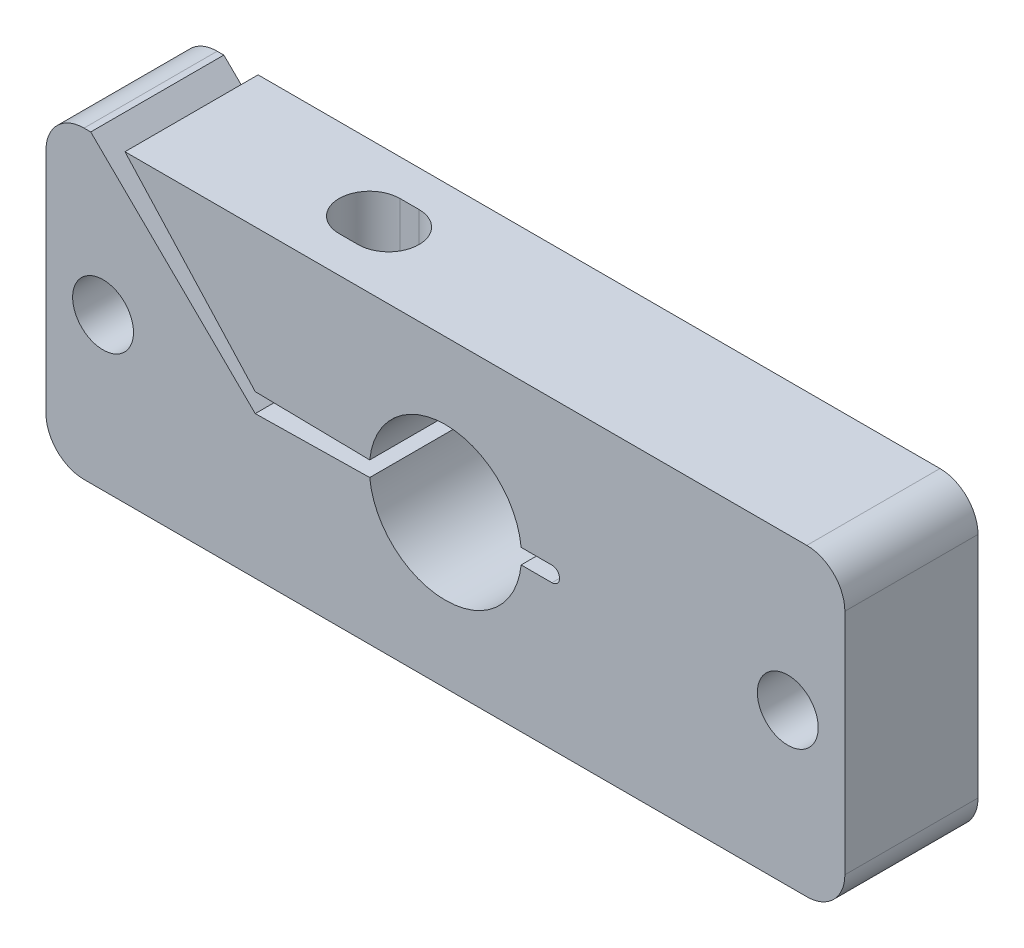
SolidWorks part; units mm, degrees
ref_plane "Front Plane" through (0, 0, 0) normal (0, 0, 1) x (1, 0, 0)
ref_plane "Top Plane" through (0, 0, 0) normal (0, 1, 0) x (1, 0, 0)
ref_plane "Right Plane" through (0, 0, 0) normal (1, 0, 0) x (0, 0, -1)
sketch "Sketch1" plane through (0, 0, 0) normal (0, 0, 1) x (1, 0, 0)
  line L0 (-43.3338, 0) -> (30.2546, 0) construction
  line L1 (-10, 0) -> (-19.1197, 9.4437) construction
  line L2 (-21, 8) -> (-18.6497, 8)
  line L3 (-21, 8) -> (-21, -8)
  line L4 (-21, -8) -> (21, -8)
  line L5 (21, 8) -> (21, -8)
  line L6 (-10, 0.5) -> (-3.9799, 0.4)
  line L7 (-10, 0.5) -> (-10, -0.5) construction
  line L8 (-10, -0.5) -> (-3.9799, -0.4)
  line L9 (6, 0.4) -> (6, -0.4)
  line L10 (-10, 0.5) -> (-16.8484, 8)
  line L11 (-10, -0.5) -> (-18.6497, 8)
  line L12 (3.9799, 0.4) -> (6, 0.4)
  line L13 (3.9799, -0.4) -> (6, -0.4)
  line L14 (-16.8484, 8) -> (21, 8)
  line L15 (0, 10.4655) -> (0, -11.9899) construction
  arc A0 (-3.9799, -0.4) -> (3.9799, -0.4) centre (0, 0) ccw
  arc A1 (3.9799, 0.4) -> (-3.9799, 0.4) centre (0, 0) ccw
  circle A2 centre (-18, 0) radius 2.2 construction
  circle A3 centre (-18, 0) radius 1.6
  circle A4 centre (18, 0) radius 1.6
  dimension "D1" = 8
  dimension "D2" = 4.4
  dimension "D4" = 3
  dimension "D5" = 36
  dimension "D7" = 2
  dimension "D16" = 3.2
  dimension "D3" = 8
  dimension "D6" = 0.8
  dimension "D8" = 46
  dimension "D9" = 6
  dimension "D10" = 1.5
  dimension "D11" = 1.6
  dimension "D14" = 0.8
  dimension "D15" = 1
extrude "Boss-Extrude1" add sketch "Sketch1" along normal blind 3.5 and the other way blind 3.5
sketch "Sketch3" plane through (0, -8, 0) normal (0, -1, 0) x (1, 0, 0)
  line L0 (-10, 3.5) -> (-3.9799, 3.5) construction
  line L1 (-21, 3.5) -> (21, 3.5) construction
  line L7 (-6.99, 2.7251) -> (-6.99, -2.5156) construction
  line L10 (21, -3.5) -> (21, 3.5) construction
  circle A0 centre (-6.99, 0) radius 2.2
  circle A1 centre (-6.99, 0) radius 1.6
  point P6 (-6.99, 3.5)
  dimension "D1" = 4.4
  dimension "D2" = 3.2
extrude "Cut-Extrude1" cut sketch "Sketch3" against normal up to next contours A1
extrude "Cut-Extrude2" cut sketch "Sketch3<3>" against normal blind 6
sketch "Sketch3<3>" plane through (0, -8, 0) normal (0, -1, 0) x (1, 0, 0) same geometry as "Sketch3"
sketch "Sketch4" plane through (0, 8, 0) normal (0, 1, 0) x (1, 0, 0)
  line L0 (-7.49, 0) -> (-6.49, 0) construction
  line L1 (-7.49, 1.6) -> (-6.49, 1.6)
  line L2 (-7.49, -1.6) -> (-6.49, -1.6)
  arc A0 (-7.49, 1.6) -> (-7.49, -1.6) centre (-7.49, 0) ccw
  arc A1 (-6.49, -1.6) -> (-6.49, 1.6) centre (-6.49, 0) ccw
  point P2 (-6.99, 0)
  dimension "D1" = 3.2
  dimension "D2" = 1
extrude "Cut-Extrude3" cut sketch "Sketch4" against normal up to next
fillet "Fillet1" radius 2 4 edges at (-21, -8, 0) (21, -8, 0) (21, 8, 0) (-21, 8, 0)
fillet "Fillet2" 2 edges at (6, 0.4, 0) (6, -0.4, 0) type full round first side face at (4.99, 0.4, 0) second side face at (4.99, -0.4, 0) middle face at (6, 0, 0)
